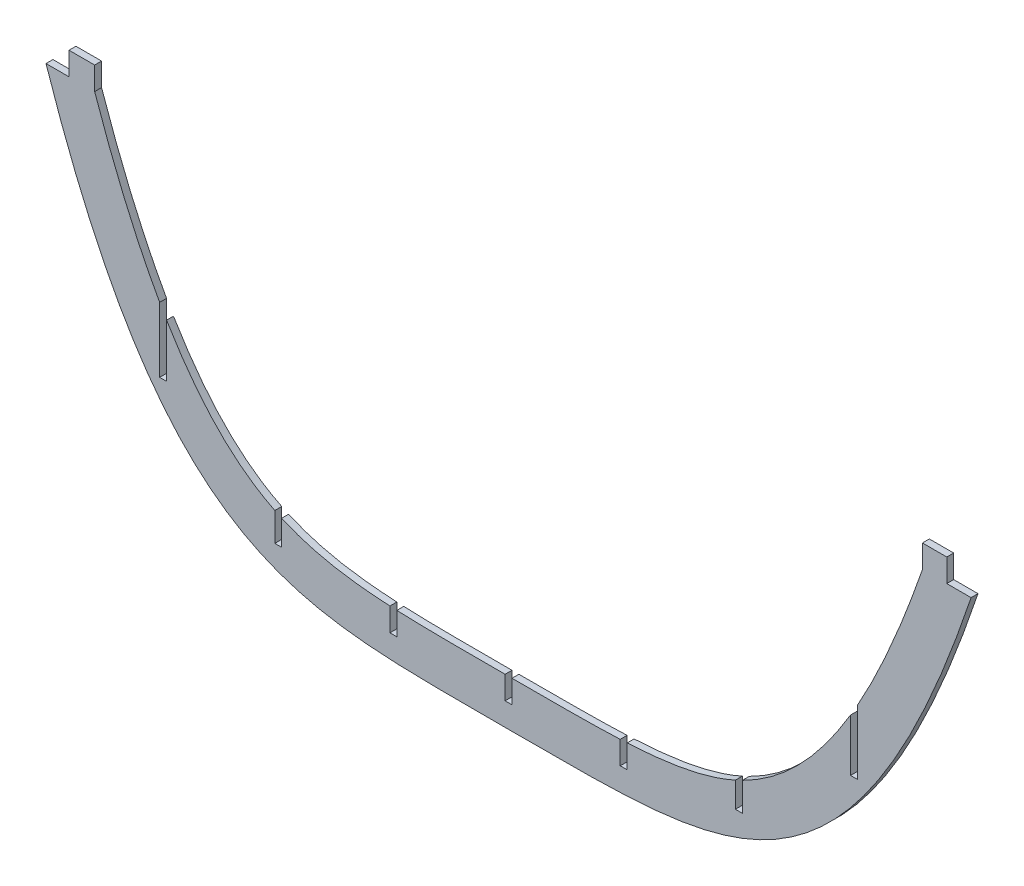
SolidWorks part; units mm, degrees
ref_plane "Front Plane" through (0, 0, 0) normal (0, 0, 1) x (1, 0, 0)
ref_plane "Top Plane" through (0, 0, 0) normal (0, 1, 0) x (1, 0, 0)
ref_plane "Right Plane" through (0, 0, 0) normal (1, 0, 0) x (0, 0, -1)
sketch "Sketch1" plane through (0, 0, 0) normal (0, 0, 1) x (1, 0, 0)
  line L5 (-190.8571, 160) -> (-179.7305, 160)
  line L6 (-179.7305, 160) -> (-179.7305, 150)
  line L8 (190.2938, 160) -> (179.7305, 160)
  line L9 (179.7305, 160) -> (179.7305, 150)
  line L10 (-200.8571, 150) -> (-190.8571, 150)
  line L11 (-190.8571, 150) -> (-190.8571, 160)
  line L12 (190.2938, 160) -> (190.2938, 150)
  line L13 (190.2938, 150) -> (200.8571, 150)
  spline S0 degree 4 poles (-216.8089, 203.6342) (-108.4044, -203.6342) (0, 203.6342) (108.4044, -203.6342) (216.8089, 203.6342) knots 0 0 0 0 0 1 1 1 1 1 construction
  spline S1 degree 4 poles (-200.8571, 150) (-100.4286, -150) (0, 150) (100.4286, -150) (200.8571, 150) knots 0.036788 0.036788 0.036788 0.036788 0.036788 0.963212 0.963212 0.963212 0.963212 0.963212
  spline S2 degree 1 poles (-181.8916, 156.3489) (181.8916, 156.3489) knots 0 0 1 1 construction
  spline S3 degree 3 poles (-181.8916, 156.3489) (-181.3891, 154.848) (-180.3653, 151.8253) (-178.3412, 145.9898) (-175.81, 138.9489) (-172.7858, 130.9351) (-168.7678, 120.7983) (-163.7768, 109.1306) (-157.8474, 96.6329) (-151.9892, 85.5414) (-144.2887, 72.4973) (-134.9007, 59.2193) (-124.0868, 47.3263) (-113.706, 38.6442) (-103.5943, 32.3808) (-93.4771, 27.8904) (-83.0914, 24.7263) (-68.685, 21.8783) (-49.5164, 20.3042) (-25.1066, 19.9753) (0, 20.0124) (25.1066, 19.9753) (49.5164, 20.3042) (68.685, 21.8783) (83.0914, 24.7263) (93.4771, 27.8904) (103.5943, 32.3808) (113.706, 38.6442) (124.0868, 47.3263) (134.9007, 59.2193) (144.2887, 72.4973) (151.9892, 85.5414) (157.8474, 96.6329) (163.7768, 109.1306) (168.7678, 120.7983) (172.7858, 130.9351) (175.81, 138.9489) (178.3412, 145.9898) (180.3653, 151.8253) (181.3891, 154.848) (181.8916, 156.3489) knots 0.036788 0.036788 0.036788 0.036788 0.040406 0.044025 0.051263 0.058501 0.065738 0.080214 0.094689 0.109165 0.12364 0.152591 0.181541 0.210492 0.239443 0.268394 0.297345 0.326295 0.384197 0.442098 0.5 0.557902 0.615803 0.673705 0.702655 0.731606 0.760557 0.789508 0.818459 0.847409 0.87636 0.890835 0.905311 0.919786 0.934262 0.941499 0.948737 0.955975 0.959594 0.963212 0.963212 0.963212 0.963212 only from (-179.7305, 150) to (179.7305, 150)
  dimension "D1" = 20
extrude "Boss-Extrude1" add sketch "Sketch1" along normal blind 3 contours S1 L13 L12 L8 L9 S3 L6 L5 L11 L10
sketch "Sketch2" plane through (0, 0, 0) normal (0, 0, 1) x (1, 0, 0)
  line L8 (1.5, 10) -> (-1.5, 10)
  line L12 (-1.5, 10) -> (-1.5, 21.3682)
  line L13 (-1.5, 21.3682) -> (1.5, 21.3682)
  line L14 (1.5, 10) -> (1.5, 21.3682)
extrude "Cut-Extrude2" cut sketch "Sketch2" along normal blind 22
sketch "Sketch4" plane through (0, 0, 0) normal (0, 0, 1) x (1, 0, 0)
  line L5 (101.5, 19.216) -> (98.5, 19.216)
  line L6 (101.5, 19.216) -> (101.5, 32.1285)
  line L7 (101.5, 32.1285) -> (98.5, 32.1285)
  line L8 (98.5, 19.216) -> (98.5, 32.1285)
extrude "Cut-Extrude3" cut sketch "Sketch4" along normal blind 45
sketch "Sketch5" plane through (0, 0, 0) normal (0, 0, 1) x (1, 0, 0)
  line L5 (-98.5, 19.216) -> (-101.5, 19.216)
  line L6 (-98.5, 19.216) -> (-98.5, 36.9515)
  line L7 (-98.5, 36.9515) -> (-101.5, 36.9515)
  line L8 (-101.5, 19.216) -> (-101.5, 36.9515)
extrude "Cut-Extrude4" cut sketch "Sketch5" along normal blind 38
sketch "Sketch6" plane through (0, 0, 0) normal (0, 0, 1) x (1, 0, 0)
  line L6 (-148.5, 56.656) -> (-151.5, 56.656)
  line L7 (-148.5, 56.656) -> (-148.5, 87.4942)
  line L8 (-148.5, 87.4942) -> (-151.5, 87.4942)
  line L9 (-151.5, 56.656) -> (-151.5, 87.4942)
extrude "Cut-Extrude5" cut sketch "Sketch6" along normal blind 99
sketch "Sketch7" plane through (0, 0, 0) normal (0, 0, 1) x (1, 0, 0)
  line L2 (148.5, 59.9497) -> (148.5, 86.6745)
  line L3 (148.5, 59.9497) -> (148.5, 56.9497)
  line L4 (148.5, 56.9497) -> (151.5, 56.9497)
  line L5 (151.5, 56.9497) -> (151.5, 59.9497)
  line L7 (151.5, 59.9497) -> (151.5, 86.6745)
  line L8 (151.5, 86.6745) -> (148.5, 86.6745)
extrude "Cut-Extrude6" cut sketch "Sketch7" along normal blind 239
sketch "Sketch8" plane through (0, 0, 3) normal (0, 0, 1) x (1, 0, 0)
  line L0 (-50, 10.576) -> (-48.5, 10.576)
  line L2 (-48.5, 10.576) -> (-48.5, 27.6116)
  line L3 (-48.5, 27.6116) -> (-51.5, 27.6116)
  line L4 (-51.5, 27.6116) -> (-51.5, 10.576)
  line L5 (-51.5, 10.576) -> (-50, 10.576)
  point P6 (0, 0)
extrude "Cut-Extrude7" cut sketch "Sketch8" against normal through all
ref_plane "Plane1" through (0, 0, 0) normal (-1, 0, 0) x (0, 0, 1)
mirror "Mirror1" about plane through (0, 0, 0) normal (-1, 0, 0) of "Cut-Extrude7"
